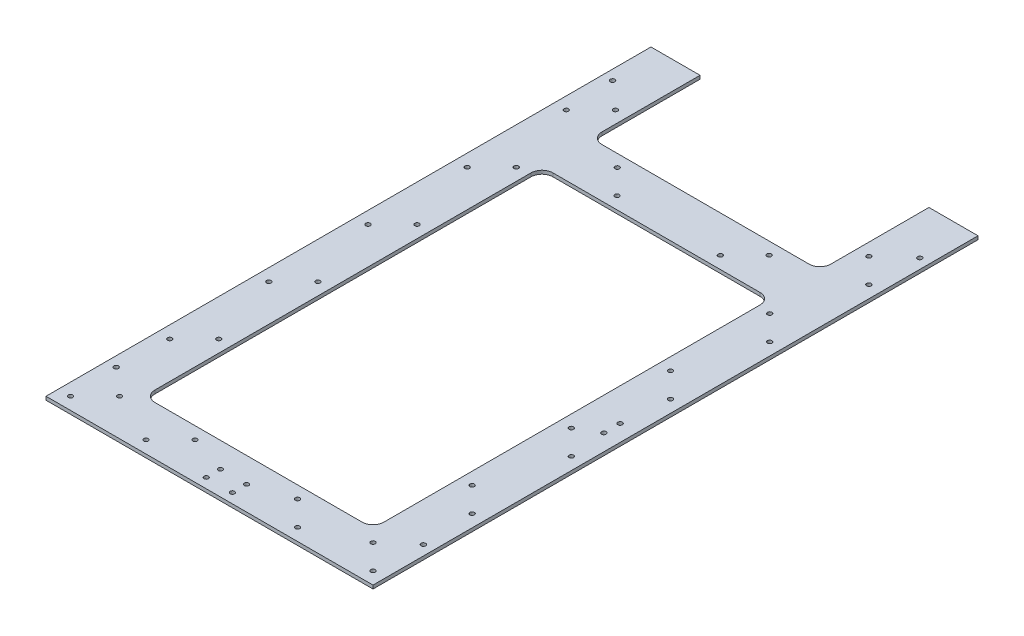
SolidWorks part; units mm, degrees
ref_plane "Front Plane" through (0, 0, 0) normal (0, 0, 1) x (1, 0, 0)
ref_plane "Top Plane" through (0, 0, 0) normal (0, 1, 0) x (1, 0, 0)
ref_plane "Right Plane" through (0, 0, 0) normal (1, 0, 0) x (0, 0, -1)
sketch "Sketch1" plane through (0, 0, 0) normal (0, 1, 0) x (1, 0, 0)
  line L1 (150, -300) -> (-150, -300)
  line L2 (150, -300) -> (150, 300)
  line L3 (150, 300) -> (-150, 300)
  line L4 (-150, -300) -> (-150, 300)
  line L5 (150, -300) -> (-150, 300) construction
  line L6 (150, 300) -> (-150, -300) construction
  point P0 (0, 0)
  dimension "D1" = 600
  dimension "D2" = 300
extrude "Boss-Extrude1" add sketch "Sketch1" along normal blind 3.175
sketch "Sketch3" plane through (0, 3.175, 0) normal (0, 1, 0) x (1, 0, 0)
  line L0 (-95, -255) -> (95, -255)
  line L1 (0, 255) -> (0, -300) construction
  line L2 (105, -245) -> (105, 100)
  line L3 (95, 110) -> (-95, 110)
  line L4 (105, 255) -> (105, 165)
  line L5 (150, 300) -> (-150, 300) construction
  line L6 (95, 155) -> (-95, 155)
  line L8 (0, -300) -> (0, -342.0806) construction
  line L9 (-105, 255) -> (-105, 165)
  line L10 (-105, -245) -> (-105, 100)
  line L11 (50.6601, -255) -> (50.6601, -300) construction
  line L12 (-150, -300) -> (150, -300) construction
  line L13 (105, 27.7939) -> (150, 27.7939) construction
  line L14 (150, -300) -> (150, 300) construction
  line L15 (-150, 27.7939) -> (-105, 27.7939) construction
  line L16 (-150, 300) -> (-150, -300) construction
  line L17 (54.6047, 155) -> (54.6047, 110) construction
  line L18 (105, 255) -> (150, 255)
  line L19 (150, 255) -> (150, 300)
  line L20 (150, 300) -> (-150, 300)
  line L21 (-150, 300) -> (-150, 255)
  line L22 (-150, 255) -> (-105, 255)
  arc A1 (-105, 165) -> (-95, 155) centre (-95, 165) ccw
  arc A3 (105, 165) -> (95, 155) centre (95, 165) cw
  arc A4 (105, 100) -> (95, 110) centre (95, 100) ccw
  arc A5 (-105, 100) -> (-95, 110) centre (-95, 100) cw
  arc A6 (-105, -245) -> (-95, -255) centre (-95, -245) ccw
  arc A7 (95, -255) -> (105, -245) centre (95, -245) ccw
  point P17 (0, 300)
  point P18 (0, 155)
  point P19 (0, 110)
  point P20 (0, -255)
  point P22 (-105.4457, 300)
  point P25 (-105, 155)
  point P28 (105.4457, 300)
  point P31 (105, 155)
  point P34 (105, 110)
  point P37 (-105, 110)
  point P40 (-105, -255)
  point P43 (105, -255)
  dimension "D1" = 45
  dimension "D4" = 10
  dimension "D2" = 45
  dimension "D3" = 145
extrude "Cut-Extrude1" cut sketch "Sketch3" against normal blind 10
sketch "Sketch4" plane through (0, 3.175, 0) normal (0, 1, 0) x (1, 0, 0)
  circle A0 centre (12, -291) radius 2.05
  circle A1 centre (-12, -291) radius 2.05
  circle A2 centre (-12, -278) radius 2.05
  circle A3 centre (12, -278) radius 2.05
  circle A4 centre (12, -291) radius 2.1 construction
  circle A5 centre (12, -278) radius 2.1 construction
  dimension "D1" = 4.1
extrude "Cut-Extrude2" cut sketch "Sketch4" against normal blind 51
sketch "Sketch5" plane through (0, 3.175, 0) normal (0, 1, 0) x (1, 0, 0)
  circle A0 centre (135, -73.2648) radius 2.1
  circle A1 centre (135, -58.2648) radius 2.1
  dimension "D1" = 4.2
extrude "Cut-Extrude3" cut sketch "Sketch5" against normal blind 67
sketch "Sketch7" plane through (0, 3.175, 0) normal (0, 1, 0) x (1, 0, 0)
  line L0 (138.75, -300) -> (138.75, 255) construction
  line L1 (116.25, -300) -> (116.25, 255) construction
  line L2 (150, -187.519) -> (138.75, -187.519) construction
  line L3 (150, -300) -> (150, 255) construction
  line L4 (138.75, -187.519) -> (127.5, -187.519) construction
  line L5 (127.5, -187.519) -> (116.25, -187.519) construction
  line L6 (116.25, -187.519) -> (105, -187.519) construction
  line L7 (105, -245) -> (105, 100) construction
  line L8 (-150, -300) -> (150, -300) construction
  line L10 (150, 121.25) -> (0, 121.25) construction
  line L11 (105, 255) -> (150, 255) construction
  line L12 (150, 143.75) -> (0, 143.75) construction
  line L13 (33.148, 155) -> (33.148, 143.75) construction
  line L14 (-95, 155) -> (95, 155) construction
  line L15 (33.148, 143.75) -> (33.148, 132.5) construction
  line L16 (33.148, 132.5) -> (33.148, 121.25) construction
  line L17 (33.148, 121.25) -> (33.148, 110) construction
  line L18 (95, 110) -> (-95, 110) construction
  line L19 (150, -288.75) -> (0, -288.75) construction
  line L20 (150, -266.25) -> (0, -266.25) construction
  line L21 (55.7313, -255) -> (55.7313, -266.25) construction
  line L22 (-95, -255) -> (95, -255) construction
  line L23 (55.7313, -266.25) -> (55.7313, -277.5) construction
  line L24 (55.7313, -277.5) -> (55.7313, -288.75) construction
  line L25 (55.7313, -288.75) -> (55.7313, -300) construction
  line L26 (-42.5408, 110) -> (-42.5408, -255) construction
  line L27 (0, -288.75) -> (0, -389.9124) construction
  circle A0 centre (138.75, -288.75) radius 2.05
  circle A1 centre (116.25, -266.25) radius 2.05
  circle A2 centre (47.0236, -266.25) radius 2.05
  circle A3 centre (69.5236, -288.75) radius 2.05
  circle A4 centre (116.25, -175.2809) radius 2.05
  circle A5 centre (138.75, -197.7809) radius 2.05
  circle A6 centre (116.25, -84.3118) radius 2.05
  circle A7 centre (138.75, -106.8118) radius 2.05
  circle A8 centre (116.25, 6.6573) radius 2.05
  circle A9 centre (138.75, -15.8427) radius 2.05
  circle A10 centre (116.25, 97.6264) radius 2.05
  circle A11 centre (138.75, 75.1264) radius 2.05
  circle A12 centre (116.25, 188.5955) radius 2.05
  circle A13 centre (138.75, 166.0955) radius 2.05
  circle A15 centre (138.75, 257.0646) radius 2.05
  circle A16 centre (47.3578, 121.25) radius 2.05
  circle A17 centre (69.635, 143.75) radius 2.05
  circle A18 centre (-47.3578, 121.25) radius 2.05
  circle A19 centre (-69.635, 143.75) radius 2.05
  circle A20 centre (-138.75, 257.0646) radius 2.05
  circle A21 centre (-116.25, 188.5955) radius 2.05
  circle A22 centre (-138.75, 166.0955) radius 2.05
  circle A23 centre (-138.75, 75.1264) radius 2.05
  circle A24 centre (-116.25, 6.6573) radius 2.05
  circle A25 centre (-116.25, 97.6264) radius 2.05
  circle A26 centre (-116.25, -84.3118) radius 2.05
  circle A27 centre (-138.75, -15.8427) radius 2.05
  circle A28 centre (-138.75, -106.8118) radius 2.05
  circle A29 centre (-116.25, -175.2809) radius 2.05
  circle A30 centre (-138.75, -197.7809) radius 2.05
  circle A31 centre (-116.25, -266.25) radius 2.05
  circle A32 centre (-138.75, -288.75) radius 2.05
  circle A33 centre (-47.0236, -266.25) radius 2.05
  circle A34 centre (-69.5236, -288.75) radius 2.05
  circle A35 centre (116.25, 279.5646) radius 2.05 [skipped]
  dimension "D1" = 4.1
  dimension "D2" = 4.1
  dimension "D3" = 2
  dimension "D4" = 7
extrude "Cut-Extrude4" cut sketch "Sketch7" against normal blind 10
sketch "Sketch8" plane through (0, 3.175, 0) normal (0, 1, 0) x (1, 0, 0)
  circle A0 centre (140.9323, 210.666) radius 2.1
  circle A1 centre (140.9323, -244.7257) radius 2.1
  dimension "D1" = 4.2
extrude "Cut-Extrude5" cut sketch "Sketch8" against normal blind 10
ref_plane "Plane1" through (0, 0, 0) normal (1, 0, 0) x (0, 0, -1)
mirror "Mirror1" about plane through (0, 0, 0) normal (1, 0, 0) of "Cut-Extrude5"
equation "\"D2@Sketch7\"=\"D1@Sketch7\""
